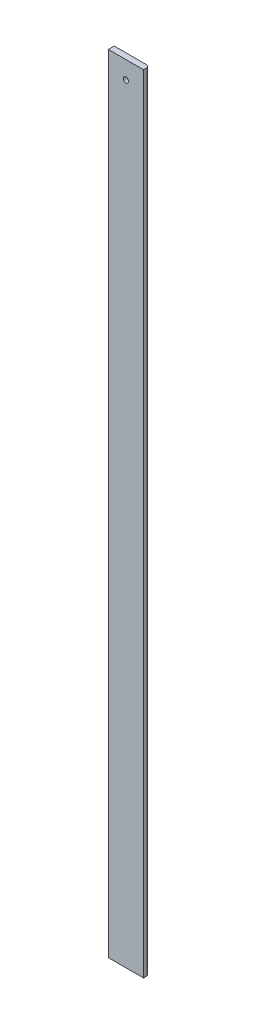
SolidWorks part; units mm, degrees
material "6061 Alloy"
ref_plane "Front Plane" through (0, 0, 0) normal (0, 0, 1) x (1, 0, 0)
ref_plane "Top Plane" through (0, 0, 0) normal (0, 1, 0) x (1, 0, 0)
ref_plane "Right Plane" through (0, 0, 0) normal (1, 0, 0) x (0, 0, -1)
sketch "Sketch2" plane through (0, 0, 0) normal (0, 1, 0) x (1, 0, 0)
  line L0 (0, 0) -> (19.05, 0)
  line L1 (0, 0) -> (0, 19.05)
  line L2 (4.7625, 3.175) -> (17.4625, 3.175)
  line L3 (3.175, 4.7625) -> (3.175, 17.4625)
  line L4 (0, 19.05) -> (1.5875, 19.05)
  line L5 (19.05, 1.5875) -> (19.05, 0)
  line L6 (3.175, 3.175) -> (3.175, 19.05) construction
  line L7 (3.175, 3.175) -> (19.05, 3.175) construction
  arc A0 (3.175, 17.4625) -> (1.5875, 19.05) centre (1.5875, 17.4625) ccw
  arc A1 (3.175, 4.7625) -> (4.7625, 3.175) centre (4.7625, 4.7625) ccw
  arc A2 (17.4625, 3.175) -> (19.05, 1.5875) centre (17.4625, 1.5875) cw
  dimension "D2" = 1.5875
  dimension "D1" = 3.175
extrude "Boss-Extrude1" add sketch "Sketch2" along normal blind 431.8
sketch "Sketch4" plane through (3.175, 0, 0) normal (1, 0, 0) x (0, 0, -1)
  line L0 (19.05, 431.8) -> (19.05, 406.4)
  line L1 (19.05, 431.8) -> (19.05, 0) construction
  line L2 (19.05, 406.4) -> (3.175, 406.4)
  line L3 (3.175, 431.8) -> (3.175, 0) construction
  line L4 (3.175, 406.4) -> (3.175, 431.8)
  line L5 (3.175, 431.8) -> (19.05, 431.8)
extrude "Cut-Extrude1" cut sketch "Sketch4" against normal blind 6.35
sketch "Sketch5" plane through (3.175, 0, 0) normal (-1, 0, 0) x (0, 0, 1)
  line L8 (-4.7625, 406.4) -> (-3.175, 406.4)
  line L9 (-3.175, 406.4) -> (-3.175, 431.8)
  line L10 (-3.175, 431.8) -> (-4.7625, 431.8)
  line L11 (-4.7625, 431.8) -> (-4.7625, 406.4)
  line L12 (-4.7625, 406.4) -> (-3.175, 406.4)
  line L13 (-3.175, 406.4) -> (-3.175, 431.8)
  line L14 (-3.175, 431.8) -> (-4.7625, 431.8)
  line L15 (-4.7625, 431.8) -> (-4.7625, 406.4)
  dimension "D1" = 0
extrude "Cut-Extrude2" cut sketch "Sketch5" against normal blind 6.35
sketch "Sketch6" plane through (3.175, 0, 0) normal (1, 0, 0) x (0, 0, -1)
  line L0 (19.05, 0) -> (3.175, 0) construction
  line L1 (11.1125, 0) -> (11.1125, 15.875) construction
  line L2 (19.05, 406.4) -> (3.175, 406.4) construction
  line L3 (11.1125, 406.4) -> (11.1125, 390.525) construction
  line L4 (11.1125, 15.875) -> (11.1125, 203.2) construction
  line L5 (11.1125, 203.2) -> (11.1125, 390.525) construction
  circle A1 centre (11.1125, 109.5375) radius 1.4224
  circle A2 centre (11.1125, 203.2) radius 1.4224
  circle A3 centre (11.1125, 296.8625) radius 1.4224
  circle A5 centre (11.1125, 11.1125) radius 1.4224
  circle A6 centre (11.1125, 395.2875) radius 1.4224
  point P12 (11.1125, 203.2)
  point P13 (11.1125, 296.8625)
  point P15 (11.1125, 109.5375)
  dimension "D2" = 2.8448
  dimension "D3" = 2.8448
  dimension "D4" = 2.8448
  dimension "D6" = 2.8448
  dimension "D7" = 2.8448
extrude "Cut-Extrude3" cut sketch "Sketch6" against normal blind 5.08
sketch "Sketch7" plane through (0, 431.8, 0) normal (0, 1, 0) x (1, 0, 0)
  line L8 (17.4625, 3.175) -> (0, 3.175)
  line L9 (0, 3.175) -> (0, 0)
  line L10 (0, 0) -> (19.05, 0)
  line L11 (19.05, 0) -> (19.05, 1.5875)
  line L12 (17.4625, 3.175) -> (0, 3.175)
  line L13 (0, 3.175) -> (0, 0)
  line L14 (0, 0) -> (19.05, 0)
  line L15 (19.05, 0) -> (19.05, 1.5875)
  arc A2 (19.05, 1.5875) -> (17.4625, 3.175) centre (17.4625, 1.5875) ccw
  arc A3 (19.05, 1.5875) -> (17.4625, 3.175) centre (17.4625, 1.5875) ccw
  dimension "D1" = 0
extrude "Cut-Extrude4" cut sketch "Sketch7" against normal blind 6.35
sketch "Sketch8" plane through (0, 0, -3.175) normal (0, 0, -1) x (-1, 0, 0)
  line L0 (0, 425.45) -> (0, 415.925) construction
  line L1 (0, 425.45) -> (0, 406.4) construction
  line L2 (0, 415.925) -> (-9.525, 415.925) construction
  circle A0 centre (-9.525, 415.925) radius 1.4224
  dimension "D1" = 2.8448
extrude "Cut-Extrude5" cut sketch "Sketch8" against normal blind 5.08
